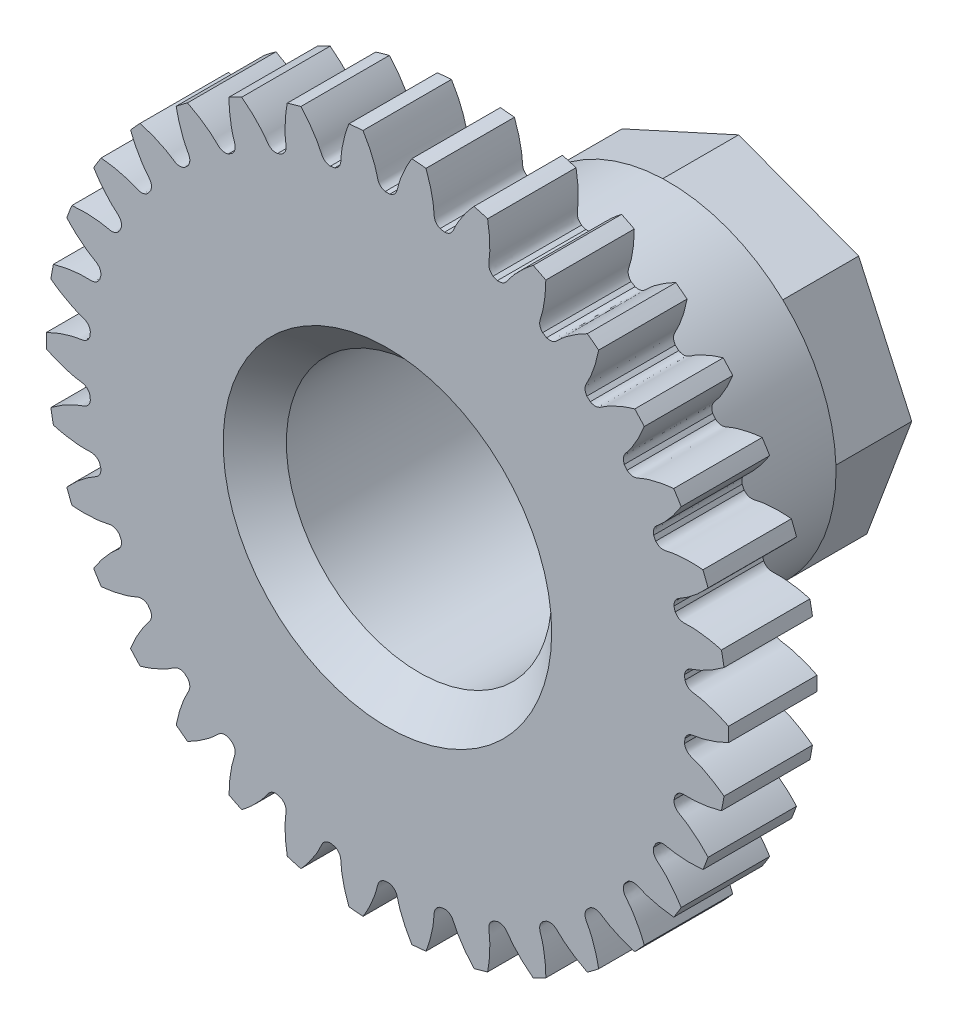
SolidWorks part; units mm, degrees
material "ABS"
ref_plane "前视基准面" through (0, 0, 0) normal (0, 0, 1) x (1, 0, 0)
ref_plane "上视基准面" through (0, 0, 0) normal (0, 1, 0) x (1, 0, 0)
ref_plane "右视基准面" through (0, 0, 0) normal (1, 0, 0) x (0, 0, -1)
sketch "草图1" plane through (0, 0, 0) normal (0, 0, 1) x (1, 0, 0)
  circle A0 centre (0, 0) radius 27
extrude "凸台-拉伸1" add sketch "草图1" along normal blind 7
ref_axis "基准轴1" through (0, 0, -1.5) along (0, 0, 1)
sketch "草图2" plane through (0, 0, 0) normal (0, 0, 1) x (1, 0, 0)
  line L0 (0, 0) -> (0, 27) construction
  circle A0 centre (0, 0) radius 27 construction
  arc A1 (0.1832, 23.6243) -> (-0.1832, 23.6243) centre (0, 0) ccw
  arc A2 (5.0574, 30.5549) -> (-5.0574, 30.5549) centre (0, 0) ccw
  spline S0 degree 3 poles (0.1832, 23.6243) (0.7166, 23.7751) (0.7634, 24.1888) (0.8799, 24.6236) (0.9129, 24.7382) (0.9511, 24.8613) (0.9947, 24.9927) (1.0441, 25.1322) (1.0997, 25.2797) (1.1618, 25.4349) (1.2307, 25.5977) (1.3068, 25.7679) (1.3903, 25.9451) (1.4816, 26.1292) (1.581, 26.32) (1.6888, 26.5172) (1.8053, 26.7204) (1.9308, 26.9296) (2.0655, 27.1443) (2.2097, 27.3642) (2.3637, 27.5892) (2.5278, 27.8188) (2.7021, 28.0528) (2.887, 28.2909) (3.0826, 28.5326) (3.2892, 28.7777) (3.5069, 29.0258) (3.7361, 29.2767) (3.9768, 29.5298) (4.2293, 29.7848) (4.5864, 30.1315) (4.8656, 30.3865) (5.0574, 30.5549) knots 0 0 0 0 0.130724 0.143504 0.157401 0.172415 0.188546 0.205794 0.224159 0.243641 0.26424 0.285956 0.308788 0.332738 0.357805 0.383988 0.411289 0.439706 0.46924 0.499892 0.53166 0.564545 0.598547 0.633666 0.669902 0.707255 0.745725 0.785312 0.826016 0.867836 0.910774 1 1 1 1
  spline S1 degree 3 poles (-0.1832, 23.6243) (-0.7166, 23.7751) (-0.7634, 24.1888) (-0.8799, 24.6236) (-0.9129, 24.7382) (-0.9511, 24.8613) (-0.9947, 24.9927) (-1.0441, 25.1322) (-1.0997, 25.2797) (-1.1618, 25.4349) (-1.2307, 25.5977) (-1.3068, 25.7679) (-1.3903, 25.9451) (-1.4816, 26.1292) (-1.581, 26.32) (-1.6888, 26.5172) (-1.8053, 26.7204) (-1.9308, 26.9296) (-2.0655, 27.1443) (-2.2097, 27.3642) (-2.3637, 27.5892) (-2.5278, 27.8188) (-2.7021, 28.0528) (-2.887, 28.2909) (-3.0826, 28.5326) (-3.2892, 28.7777) (-3.5069, 29.0258) (-3.7361, 29.2767) (-3.9768, 29.5298) (-4.2293, 29.7848) (-4.5864, 30.1315) (-4.8656, 30.3865) (-5.0574, 30.5549) knots 0 0 0 0 0.130724 0.143504 0.157401 0.172415 0.188546 0.205794 0.224159 0.243641 0.26424 0.285956 0.308788 0.332738 0.357805 0.383988 0.411289 0.439706 0.46924 0.499892 0.53166 0.564545 0.598547 0.633666 0.669902 0.707255 0.745725 0.785312 0.826016 0.867836 0.910774 1 1 1 1
extrude "切除-拉伸1" cut sketch "草图2" along normal through all
pattern_circular "阵列(圆周)1" count 34 every 10.588 about axis through (0, 0, -1.5) along (0, 0, 1) of "切除-拉伸1"
sketch "草图3" plane through (0, 0, 0) normal (0, 0, 1) x (1, 0, 0)
  circle A0 centre (0, 0) radius 25.5 construction
  dimension "Dn" = 51
sketch "草图5" plane through (0, 0, 7) normal (0, 0, 1) x (1, 0, 0)
  circle A0 centre (0, 0) radius 21
  dimension "D1" = 42
extrude "凸台-拉伸2" add sketch "草图5" against normal blind 1 from surface starting at face at (0, 0, 0)
sketch "草图4" plane through (0, 0, 7) normal (0, 0, 1) x (1, 0, 0)
  circle A0 centre (0, 0) radius 10.5
  dimension "D1" = 21
extrude "切除-拉伸2" cut sketch "草图4" against normal through all
chamfer "倒角1" distance 2.5 angle 45 1 edges at (10.5, 0, 7)
sketch "草图6" plane through (0, 0, 7) normal (0, 0, 1) x (1, 0, 0)
  circle A0 centre (0, 0) radius 10.5
  circle A1 centre (0, 0) radius 13.25
  dimension "D1" = 21
  dimension "D2" = 26.5
extrude "凸台-拉伸3" add sketch "草图6" against normal blind 20.25 from surface starting at face at (10.5, 0, -1)
chamfer "倒角2" distance 3 angle 45 1 edges at (13.25, 0, -1)
sketch "草图7" plane through (0, 0, -21.25) normal (0, 0, -1) x (-1, 0, 0)
  line L0 (0.4574, 13.2421) -> (-9.0402, 9.687)
  line L1 (-9.0402, 9.687) -> (-13.2421, 0.4574)
  line L2 (-13.2421, 0.4574) -> (-9.687, -9.0402)
  line L3 (-9.687, -9.0402) -> (-0.4574, -13.2421)
  line L4 (-0.4574, -13.2421) -> (9.0402, -9.687)
  line L5 (9.0402, -9.687) -> (13.2421, -0.4574)
  line L6 (13.2421, -0.4574) -> (9.687, 9.0402)
  line L7 (9.687, 9.0402) -> (0.4574, 13.2421)
  circle A0 centre (0, 0) radius 13.25 construction
  circle A1 centre (0, 0) radius 13.25 construction
extrude "切除-拉伸3" cut sketch "草图7" against normal blind 6 flip side to cut
